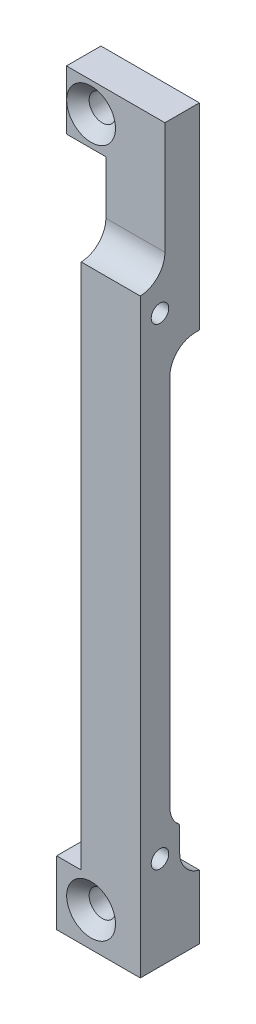
SolidWorks part; units mm, degrees
material "6061-T6 (SS)"
ref_plane "Front Plane" through (0, 0, 0) normal (0, 0, 1) x (1, 0, 0)
ref_plane "Top Plane" through (0, 0, 0) normal (0, 1, 0) x (1, 0, 0)
ref_plane "Right Plane" through (0, 0, 0) normal (1, 0, 0) x (0, 0, -1)
sketch "Sketch1" plane through (0, 0, 0) normal (0, 0, 1) x (1, 0, 0)
  line L0 (0, -93.98) -> (0, -7.62)
  line L1 (0, -55) -> (0, 55) construction
  line L2 (0, -93.98) -> (7.62, -93.98)
  line L3 (7.62, -93.98) -> (7.62, -7.62)
  line L4 (7.62, -7.62) -> (12.7, -7.62)
  line L5 (12.7, -7.62) -> (12.7, 0)
  line L6 (55, 0) -> (-55, 0) construction
  line L7 (-5.08, 0) -> (12.7, 0)
  line L8 (0, -7.62) -> (-5.08, -7.62)
  line L9 (-5.08, -7.62) -> (-5.08, 0)
  dimension "D1" = 7.62
  dimension "D3" = 7.62
  dimension "D4" = 5.08
extrude "Boss-Extrude1" add sketch "Sketch1" along normal blind 7.62
sketch "Sketch11" plane through (0, 0, 7.62) normal (0, 0, 1) x (1, 0, 0)
  line L0 (12.7, -7.62) -> (12.7, 0) construction
  line L1 (-5.08, 0) -> (12.7, 0)
  line L2 (-5.08, 0) -> (-5.08, -17.78)
  line L3 (-5.08, -17.78) -> (12.7, -17.78)
  line L4 (12.7, 0) -> (12.7, -17.78)
  dimension "D1" = 17.78
extrude "Cut-Extrude1" cut sketch "Sketch11" against normal blind 3.175
sketch "Sketch12" plane through (7.62, 0, 0) normal (1, 0, 0) x (0, 0, -1)
  line L0 (0, -93.98) -> (0, -7.62) construction
  line L1 (0, -25.4) -> (-3.81, -25.4)
  line L2 (0, -25.4) -> (0, -85.725)
  line L3 (0, -85.725) -> (-3.81, -85.725)
  line L4 (-3.81, -25.4) -> (-3.81, -85.725)
  line L6 (-7.62, -93.98) -> (0, -93.98) construction
  line L7 (-4.445, -17.78) -> (-7.62, -17.78) construction
  dimension "D1" = 3.81
  dimension "D2" = 7.62
  dimension "D3" = 8.255
extrude "Cut-Extrude2" cut sketch "Sketch12" against normal through all
ref_plane "Plane1" through (3.81, 0, 0) normal (1, 0, 0) x (0, 0, -1)
sketch "Sketch14" plane through (7.62, 0, 0) normal (1, 0, 0) x (0, 0, -1)
  line L1 (0, -85.725) -> (-7.62, -85.725)
  line L2 (0, -85.725) -> (0, -93.98)
  line L3 (0, -93.98) -> (-7.62, -93.98)
  line L4 (-7.62, -85.725) -> (-7.62, -93.98)
extrude "Boss-Extrude3" add sketch "Sketch14" along normal blind 3.175
mirror "Mirror1" about plane through (3.81, 0, 0) normal (1, 0, 0) of "Boss-Extrude3"
sketch "Sketch13" plane through (0, 0, 4.445) normal (0, 0, 1) x (1, 0, 0)
  line L2 (9.525, -3.81) -> (3.81, -3.81) construction
  line L3 (3.81, -3.81) -> (3.81, 0) construction
  line L4 (12.7, 0) -> (-5.08, 0) construction
  line L5 (3.81, -3.81) -> (-1.905, -3.81) construction
  dimension "D1" = 5.715
sketch "Sketch15" plane through (0, 0, 7.62) normal (0, 0, 1) x (1, 0, 0)
  line L0 (9.525, -3.81) -> (3.81, -3.81) construction
  line L2 (3.81, -89.535) -> (1.27, -89.535) construction
  line L4 (3.81, -93.98) -> (3.81, -89.535) construction
  line L5 (-3.175, -93.98) -> (10.795, -93.98) construction
  line L6 (3.81, -89.535) -> (6.35, -89.535) construction
  dimension "D1" = 85.725
  dimension "D2" = 3.175
sketch "Sketch24" plane through (0, 0, 3.81) normal (0, 0, -1) x (-1, 0, 0)
  line L1 (-7.62, -85.725) -> (0, -85.725)
  line L2 (-7.62, -85.725) -> (-7.62, -79.375)
  line L3 (-7.62, -79.375) -> (0, -79.375)
  line L4 (0, -85.725) -> (0, -79.375)
  line L5 (0, -25.4) -> (0, -85.725) construction
  dimension "D1" = 6.35
extrude "Boss-Extrude4" add sketch "Sketch24" along normal blind 1.27
hole_wizard "CSK for M3 Flat Head Machine Screw2" positions "Sketch17" profile "Sketch16" countersink size "M3" standard "Ansi Metric" end condition through all
sketch "Sketch17" plane through (0, 0, 7.62) normal (0, 0, 1) x (1, 0, 0)
  point P4 (1.27, -89.535)
sketch "Sketch16" plane through (1.27, -89.535, 7.62) normal (1, 0, 0) x (0, -1, 0)
  line L0 (0, 0) -> (0, 7.62)
  line L1 (0, 7.62) -> (1.7, 7.62)
  line L2 (1.7, 7.62) -> (1.7, 1.45)
  line L3 (1.7, 1.45) -> (3.15, 0)
  line L5 (3.15, 0) -> (0, 0)
  line L6 (-1.7, 1.45) -> (-3.15, 0) construction
  line L11 (0, -6.35) -> (0, 107.95) construction
  dimension "Thru Hole Dia." = 3.4
  dimension "Thru Hole Depth" = 7.62
  dimension "Near C'Sink Dia." = 6.3
  dimension "Near C'Sink Angle" = 90
hole_wizard "CSK for M3 Flat Head Machine Screw3" positions "Sketch19" profile "Sketch18" countersink size "M3" standard "Ansi Metric" end condition through all
sketch "Sketch19" plane through (0, 0, 4.445) normal (0, 0, 1) x (1, 0, 0)
  point P4 (-1.905, -3.81)
sketch "Sketch18" plane through (-1.905, -3.81, 4.445) normal (1, 0, 0) x (0, -1, 0)
  line L0 (0, 0) -> (0, 4.445)
  line L1 (0, 4.445) -> (1.7, 4.445)
  line L2 (1.7, 4.445) -> (1.7, 1.45)
  line L3 (1.7, 1.45) -> (3.15, 0)
  line L5 (3.15, 0) -> (0, 0)
  line L6 (-1.7, 1.45) -> (-3.15, 0) construction
  line L11 (0, -6.35) -> (0, 107.95) construction
  dimension "Thru Hole Dia." = 3.4
  dimension "Thru Hole Depth" = 4.445
  dimension "Near C'Sink Dia." = 6.3
  dimension "Near C'Sink Angle" = 90
sketch "Sketch20" plane through (7.62, 0, 0) normal (1, 0, 0) x (0, 0, -1)
  line L0 (-7.62, -20.9677) -> (-5.08, -20.9677) construction
  line L1 (-7.62, -85.725) -> (-7.62, -17.78) construction
  line L2 (-7.62, -81.9277) -> (-5.08, -81.9277) construction
  line L3 (-5.08, -20.9677) -> (-5.08, -81.9277) construction
  dimension "D1" = 17.1577
  dimension "D2" = 2.54
  dimension "D3" = 60.96
hole_wizard "#4-40 Tapped Hole2" positions "Sketch22" profile "Sketch21" tap size "#4-40" standard "Ansi Inch"
sketch "Sketch22" plane through (7.62, 0, 0) normal (1, 0, 0) x (0, 0, -1)
  point P1 (-5.08, -20.9677)
  point P6 (-5.08, -81.9277)
sketch "Sketch21" plane through (7.62, -20.9677, 5.08) normal (0, 1, 0) x (0, 0, -1)
  line L0 (0, 0) -> (0, 9.5438)
  line L1 (0, 9.5438) -> (1.1303, 8.8646)
  line L2 (1.1303, 8.8646) -> (1.1303, 0)
  line L5 (1.1303, 0) -> (0, 0)
  line L10 (0, 9.5438) -> (-1.1303, 8.8646) construction
  line L11 (0, -6.35) -> (0, 107.95) construction
  dimension "Tap Drill Dia." = 2.2606
  dimension "Tap Drill Depth" = 8.8646
  dimension "Drill Angle" = 118
cosmetic thread "Hole Thread2" parameters "D1"=5.6896, "D2"=2.8448
cosmetic thread "Hole Thread3" parameters "D1"=5.6896, "D2"=2.8448
sketch "Sketch25" plane through (0, 0, 0) normal (0, 0, -1) x (-1, 0, 0)
  line L0 (3.175, -93.98) -> (-10.795, -93.98) construction
  line L1 (-12.7, 0) -> (-7.62, 0)
  line L2 (-12.7, 0) -> (-12.7, -93.98)
  line L3 (-12.7, -93.98) -> (-7.62, -93.98)
  line L4 (-7.62, 0) -> (-7.62, -93.98)
extrude "Cut-Extrude3" cut sketch "Sketch25" against normal through all
fillet "Fillet1" radius 3.302 4 edges at (3.81, -85.725, 2.54) (3.81, -79.375, 3.81) (3.81, -25.4, 3.81) (3.81, -17.78, 4.445)
sketch "Sketch26" plane through (0, -93.98, 0) normal (0, -1, 0) x (1, 0, 0)
  line L0 (-3.175, 0) -> (-28.575, 0) construction
  dimension "D1" = 25.4
